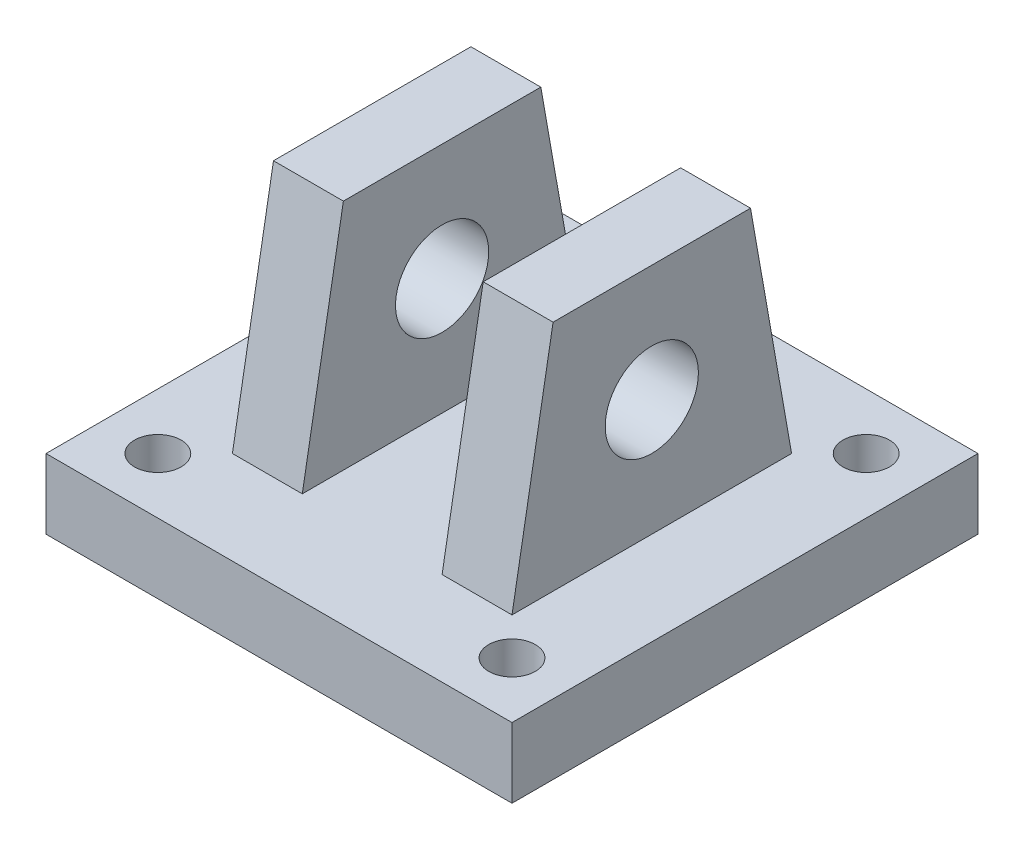
SolidWorks part; units mm, degrees
ref_plane "Front Plane" through (0, 0, 0) normal (0, 0, 1) x (1, 0, 0)
ref_plane "Top Plane" through (0, 0, 0) normal (0, 1, 0) x (1, 0, 0)
ref_plane "Right Plane" through (0, 0, 0) normal (1, 0, 0) x (0, 0, -1)
sketch "Sketch1" plane through (0, 0, 0) normal (0, 1, 0) x (1, 0, 0)
  line L1 (-63.5, 63.5) -> (63.5, 63.5)
  line L2 (-63.5, 63.5) -> (-63.5, -63.5)
  line L3 (-63.5, -63.5) -> (63.5, -63.5)
  line L4 (63.5, 63.5) -> (63.5, -63.5)
  dimension "D1" = 63.5
  dimension "D2" = 127
  dimension "D3" = 63.5
  dimension "D4" = 127
extrude "Extrude1" add sketch "Sketch1" against normal blind 19.05
sketch "Sketch2" plane through (0, 0, 0) normal (1, 0, 0) x (0, 0, -1)
  line L0 (38.1, 0) -> (26.9032, 63.5)
  line L1 (-63.5, 0) -> (63.5, 0) construction
  line L2 (26.9032, 63.5) -> (-26.9032, 63.5)
  line L3 (-26.9032, 63.5) -> (-38.1, 0)
  line L4 (63.5, -19.05) -> (63.5, 0) construction
  line L5 (-63.5, -19.05) -> (-63.5, 0) construction
  line L6 (-38.1, 0) -> (38.1, 0)
  dimension "D1" = 63.5
  dimension "D2" = 25.4
  dimension "D3" = 25.4
  dimension "D4" = 100
  dimension "D5" = 100
extrude "Extrude2" add sketch "Sketch2" along normal mid plane 76.2
sketch "Sketch3" plane through (0, 0, 0) normal (1, 0, 0) x (0, 0, -1)
  line L0 (-38.1, 0) -> (38.1, 0) construction
  circle A0 centre (0, 31.75) radius 12.7
  dimension "D1" = 25.4
  dimension "D2" = 31.75
extrude "Cut-Extrude1" cut sketch "Sketch3" against normal mid plane 76.2
sketch "Sketch4" plane through (0, 0, 0) normal (0, 0, 1) x (1, 0, 0)
  line L0 (38.1, 63.5) -> (-38.1, 63.5) construction
  line L1 (-19.05, 63.5) -> (19.05, 63.5)
  line L2 (-19.05, 63.5) -> (-19.05, 0)
  line L3 (-19.05, 0) -> (19.05, 0)
  line L4 (19.05, 63.5) -> (19.05, 0)
  line L5 (-63.5, 0) -> (63.5, 0) construction
  line L6 (-38.1, 63.5) -> (-38.1, 0) construction
  line L7 (38.1, 63.5) -> (38.1, 0) construction
  dimension "D1" = 19.05
  dimension "D2" = 19.05
extrude "Cut-Extrude2" cut sketch "Sketch4" against normal mid plane 76.2
sketch "Sketch5" plane through (0, 0, 0) normal (0, 1, 0) x (1, 0, 0)
  line L0 (-63.5, 63.5) -> (-63.5, -63.5) construction
  line L1 (63.5, 63.5) -> (-63.5, 63.5) construction
  circle A0 centre (-48.26, 48.26) radius 6.35
  dimension "D1" = 12.7
  dimension "D2" = 15.24
  dimension "D3" = 15.24
extrude "Cut-Extrude3" cut sketch "Sketch5" against normal up to next
sketch "Sketch6" plane through (0, 0, 0) normal (0, 1, 0) x (1, 0, 0)
  line L0 (63.5, -63.5) -> (63.5, 63.5) construction
  line L1 (63.5, 63.5) -> (-63.5, 63.5) construction
  circle A0 centre (48.26, 48.26) radius 6.35
  dimension "D1" = 12.7
  dimension "D2" = 15.24
  dimension "D3" = 15.24
extrude "Cut-Extrude4" cut sketch "Sketch6" against normal up to next
sketch "Sketch8" plane through (0, 0, 0) normal (0, 1, 0) x (1, 0, 0)
  line L0 (-63.5, 63.5) -> (-63.5, -63.5) construction
  line L1 (-63.5, -63.5) -> (63.5, -63.5) construction
  line L2 (63.5, -63.5) -> (63.5, 63.5) construction
  circle A0 centre (-48.26, -48.26) radius 6.35
  circle A1 centre (48.26, -48.26) radius 6.35
  dimension "D1" = 12.7
  dimension "D2" = 12.7
  dimension "D3" = 15.24
  dimension "D4" = 15.24
  dimension "D5" = 15.24
  dimension "D6" = 15.24
extrude "Cut-Extrude5" cut sketch "Sketch8" against normal up to next
